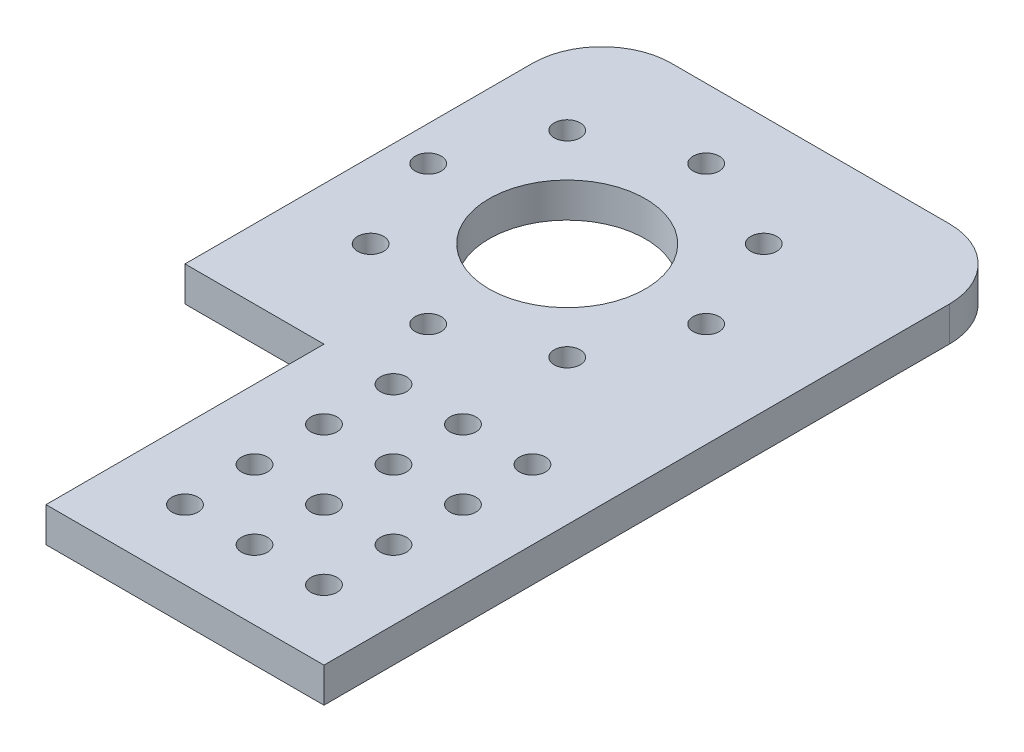
SolidWorks part; units mm, degrees
ref_plane "Front Plane" through (0, 0, 0) normal (0, 0, 1) x (1, 0, 0)
ref_plane "Top Plane" through (0, 0, 0) normal (0, 1, 0) x (1, 0, 0)
ref_plane "Right Plane" through (0, 0, 0) normal (1, 0, 0) x (0, 0, -1)
sketch "Sketch1" plane through (0, 0, 0) normal (0, 1, 0) x (1, 0, 0)
  line L1 (0, 0) -> (50.8, 0)
  line L2 (0, 0) -> (0, 50.8)
  line L3 (-25.4, 127) -> (50.8, 127)
  line L4 (50.8, 0) -> (50.8, 127)
  line L7 (0, 50.8) -> (-25.4, 50.8)
  line L8 (-25.4, 127) -> (-25.4, 50.8)
  circle A0 centre (12.7, 12.7) radius 2.3813
  circle A3 centre (25.4, 12.7) radius 2.3812
  circle A4 centre (38.1, 12.7) radius 2.3812
  circle A5 centre (25.4, 25.4) radius 2.3812
  circle A6 centre (38.1, 25.4) radius 2.3812
  circle A7 centre (25.4, 38.1) radius 2.3813
  circle A8 centre (38.1, 38.1) radius 2.3812
  circle A15 centre (12.7, 25.4) radius 2.3813
  circle A16 centre (12.7, 38.1) radius 2.3813
  circle A26 centre (6.35, 88.9) radius 14.2875
  circle A27 centre (12.7, 50.8) radius 2.3812
  circle A28 centre (25.4, 50.8) radius 2.3812
  circle A29 centre (38.1, 50.8) radius 2.3813
  dimension "D1" = 12.7
  dimension "D3" = 4.7625
  dimension "D4" = 3
  dimension "D11" = 28.575
  dimension "D7" = 127
  dimension "D2" = 12.7
  dimension "D6" = 12.7
  dimension "D8" = 12.7
  dimension "D9" = 12.7
  dimension "D10" = 50.8
  dimension "D12" = 38.1
  dimension "D13" = 31.75
  dimension "D14" = 25.4
  dimension "D5" = 4
extrude "Boss-Extrude1" add sketch "Sketch1" along normal blind 6.35
fillet "Fillet1" radius 12.7 2 edges at (-25.4, 3.175, -127) (50.8, 3.175, -127)
sketch "Sketch2" plane through (0, 6.35, 0) normal (0, 1, 0) x (1, 0, 0)
  line L0 (6.35, 88.9) -> (-19.05, 88.9) construction
  line L1 (6.35, 88.9) -> (-11.6105, 106.8605) construction
  circle A0 centre (6.35, 88.9) radius 25.4 construction
  circle A1 centre (-19.05, 88.9) radius 2.3813
  circle A2 centre (-11.6105, 106.8605) radius 2.3812
  circle A3 centre (6.35, 114.3) radius 2.3812
  circle A4 centre (24.3105, 106.8605) radius 2.3812
  circle A5 centre (31.75, 88.9) radius 2.3812
  circle A6 centre (24.3105, 70.9395) radius 2.3812
  circle A7 centre (6.35, 63.5) radius 2.3812
  circle A8 centre (-11.6105, 70.9395) radius 2.3812
  dimension "D1" = 50.8
  dimension "D2" = 4.7625
  dimension "D4" = 45
  dimension "D3" = 8
extrude "Cut-Extrude1" cut sketch "Sketch2" against normal through all
